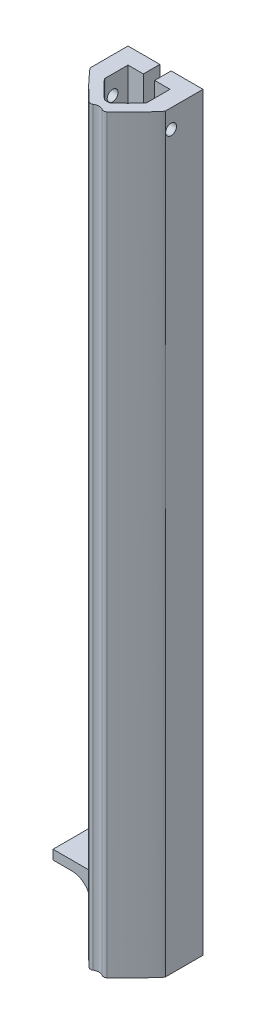
SolidWorks part; units mm, degrees
ref_plane "Front Plane" through (0, 0, 0) normal (0, 0, 1) x (1, 0, 0)
ref_plane "Top Plane" through (0, 0, 0) normal (0, 1, 0) x (1, 0, 0)
ref_plane "Right Plane" through (0, 0, 0) normal (1, 0, 0) x (0, 0, -1)
sketch "Sketch1" plane through (0, 0, 0) normal (0, 1, 0) x (1, 0, 0)
  line L0 (4.4, -15.6) -> (15.6, -15.6)
  line L1 (0, 0) -> (20, 0)
  line L2 (0, 0) -> (0, -20)
  line L3 (0, -20) -> (20, -20)
  line L4 (20, 0) -> (20, -20)
  line L5 (15.6, -4.4) -> (15.6, -15.6)
  line L6 (4.4, -4.4) -> (15.6, -4.4)
  line L7 (4.4, -4.4) -> (4.4, -15.6)
  dimension "D1" = 20
  dimension "D2" = 20
  dimension "D3" = 4.4
extrude "Boss-Extrude1" add sketch "Sketch1" along normal blind 200
sketch "Sketch2" plane through (0, 0, 0) normal (-1, 0, 0) x (0, 0, 1)
  line L0 (0, 200) -> (0, 0) construction
  line L1 (0, 200) -> (20, 200) construction
  circle A0 centre (8.5, 195) radius 1.45
  dimension "D1" = 2.9
  dimension "D2" = 8.5
  dimension "D3" = 5
extrude "Cut-Extrude1" cut sketch "Sketch2" against normal through all
fillet "Fillet3" radius 5 2 edges at (4.4, 100, 15.6) (15.6, 100, 15.6) conic rho 0.05
fillet "Fillet4" radius 10 2 edges at (0, 100, 20) (20, 100, 20) conic rho 0.05
sketch "Sketch4" plane through (0, 200, 0) normal (0, 1, 0) x (1, 0, 0)
  circle A0 centre (10, -20) radius 2.25
  dimension "D1" = 4.5
extrude "Cut-Extrude3" cut sketch "Sketch4" against normal through all
fillet "Fillet6" radius 1 2 edges
sketch "Sketch5" plane through (0, 0, 0) normal (0, 0, -1) x (-1, 0, 0)
  line L0 (-20, 200) -> (0, 200) construction
  line L1 (-8.5, 200) -> (-11.5, 200)
  line L2 (-8.5, 200) -> (-8.5, 180)
  line L3 (-8.5, 180) -> (-11.5, 180)
  line L4 (-11.5, 200) -> (-11.5, 180)
  point P6 (-10, 200)
  point P7 (-10, 200)
  dimension "D1" = 3
  dimension "D2" = 0
  dimension "D3" = 20
extrude "Cut-Extrude4" cut sketch "Sketch5" against normal blind 10
fillet "Fillet7" radius 2 1 edges at (10, 180, 0) conic rho 0.05
sketch "Sketch7" plane through (0, 0, 0) normal (0, -1, 0) x (-1, 0, 0)
  line L0 (-9.4, -15.6) -> (-10.6, -15.6) construction
  circle A0 centre (-10, -16.7) radius 0.5
  dimension "D1" = 1
  dimension "D2" = 1.1
extrude "Cut-Extrude6" cut sketch "Sketch7" against normal blind 5
sketch "Sketch8" plane through (0, 0, 0) normal (-1, 0, 0) x (0, 0, 1)
  line L0 (0, 200) -> (0, 0) construction
  line L1 (0, 14.5) -> (10, 14.5)
  line L2 (0, 14.5) -> (0, 12)
  line L3 (0, 12) -> (10, 12)
  line L4 (10, 14.5) -> (10, 12)
  line L5 (10, 0) -> (10, 200) construction
  line L6 (0, 0) -> (10, 0) construction
  dimension "D1" = 2.5
  dimension "D2" = 12
extrude "Boss-Extrude2" add sketch "Sketch8" along normal blind 10
fillet "Fillet8" radius 5 1 edges
equation "\"滑动-垂直孔\"= 0.6"
equation "\"滑动-水平孔\"= 0.3"
equation "\"松动-垂直孔\"= 0.3"
equation "\"松动-水平孔\"= 0.1"
equation "\"正常-垂直孔\"= 0.15"
equation "\"正常-水平孔\"= 0"
equation "\"紧缩-垂直孔\"= 0"
equation "\"紧缩-水平孔\"= - 0.1"
equation "\"D3@Sketch1\"=5-\"滑动-垂直孔\""
equation "\"D1@Sketch2\"=\"紧缩-水平孔\"+3"
equation "\"D2@Sketch2\"=\"D2@Sketch1\"/2 -1.5"
